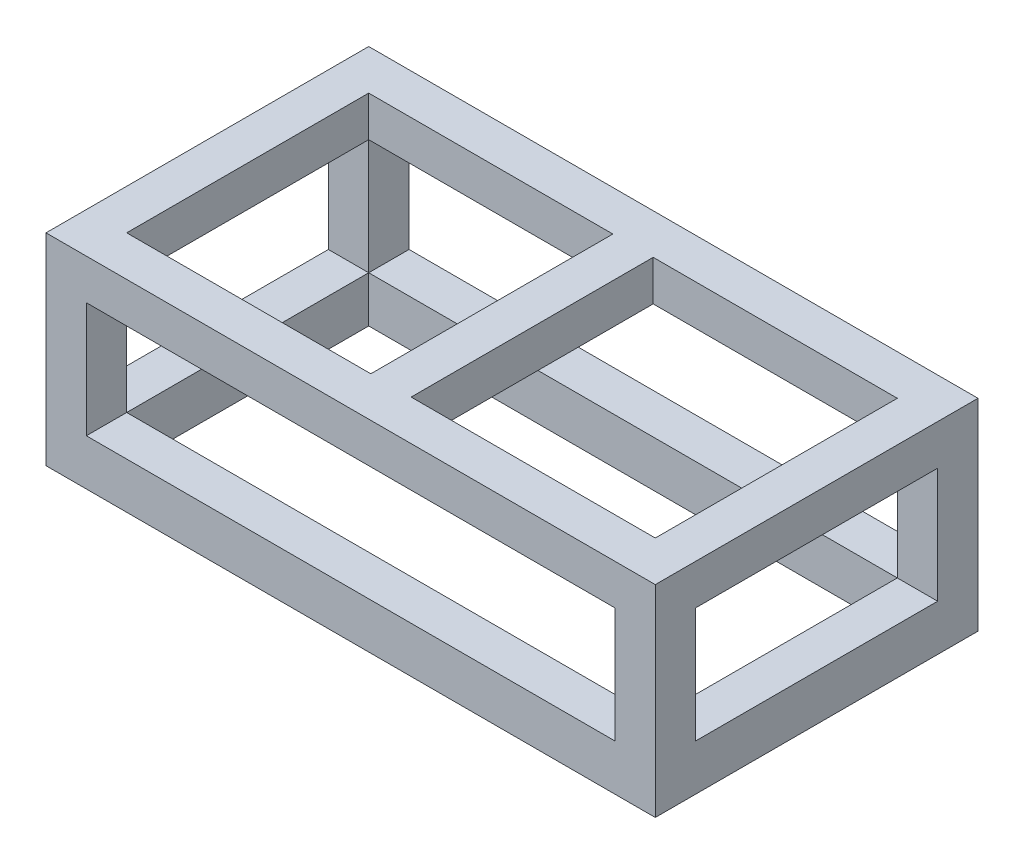
SolidWorks part; units mm, degrees
ref_plane "Front Plane" through (0, 0, 0) normal (0, 0, 1) x (1, 0, 0)
ref_plane "Top Plane" through (0, 0, 0) normal (0, 1, 0) x (1, 0, 0)
ref_plane "Right Plane" through (0, 0, 0) normal (1, 0, 0) x (0, 0, -1)
ref_plane "Plane1" through (0, -266, 0) normal (0, 1, 0) x (1, 0, 0)
sketch "Sketch2" plane through (0, -266, 0) normal (0, 1, 0) x (1, 0, 0)
  line L0 (-105, 105) -> (-105, -105)
  line L1 (-140, 140) -> (388.6432, 140)
  line L2 (-140, 140) -> (-140, -140)
  line L3 (-140, -140) -> (388.6432, -140)
  line L4 (388.6432, 140) -> (388.6432, -140)
  line L5 (-105, -105) -> (353.6432, -105)
  line L6 (353.6432, 105) -> (353.6432, -105)
  line L7 (-105, 105) -> (353.6432, 105)
  line L8 (106.8216, -105) -> (106.8216, 105)
  line L9 (141.8216, -105) -> (141.8216, 105)
  line L10 (124.3216, 105) -> (124.3216, -105) construction
  dimension "D2" = 35
  dimension "D1" = 35
extrude "Boss-Extrude1" add sketch "Sketch2" against normal blind 35 contours L4 L1 L2 L3 L0 L7 L6 L5 | L7 L10 L5 L9 | L10 L7 L8 L5 region at (115.5716, -266, 0) region at (133.0716, -266, 0) region at (124.3216, -266, -134.0178)
sketch "Sketch3" plane through (0, -301, 0) normal (0, -1, 0) x (-1, 0, 0)
  line L1 (140, -140) -> (105, -140)
  line L2 (140, -140) -> (140, -105)
  line L3 (140, -105) -> (105, -105)
  line L4 (105, -140) -> (105, -105)
  line L5 (140, 140) -> (105, 140)
  line L6 (140, 140) -> (140, 105)
  line L7 (140, 105) -> (105, 105)
  line L8 (105, 140) -> (105, 105)
  line L9 (-353.6432, 105) -> (-388.6432, 105)
  line L10 (-353.6432, 105) -> (-353.6432, 140)
  line L11 (-353.6432, 140) -> (-388.6432, 140)
  line L12 (-388.6432, 105) -> (-388.6432, 140)
  line L13 (-353.6432, -105) -> (-388.6432, -105)
  line L14 (-353.6432, -105) -> (-353.6432, -140)
  line L15 (-353.6432, -140) -> (-388.6432, -140)
  line L16 (-388.6432, -105) -> (-388.6432, -140)
extrude "Boss-Extrude2" add sketch "Sketch3" along normal blind 100
shell "Shell1" thickness 2 removed face at (-122.5, -401, 122.5) removed face at (-122.5, -401, -122.5) removed face at (371.1432, -401, 122.5) removed face at (371.1432, -401, -122.5)
sketch "Sketch4" plane through (0, -401, 0) normal (0, -1, 0) x (1, 0, 0)
  line L1 (-140, 140) -> (388.6432, 140)
  line L2 (-140, 140) -> (-140, -140)
  line L3 (-140, -140) -> (388.6432, -140)
  line L4 (388.6432, 140) -> (388.6432, -140)
  line L5 (353.6432, -105) -> (-105, -105)
  line L6 (353.6432, -105) -> (353.6432, 105)
  line L7 (353.6432, 105) -> (-105, 105)
  line L8 (-105, -105) -> (-105, 105)
extrude "Boss-Extrude3" add sketch "Sketch4" along normal blind 40
